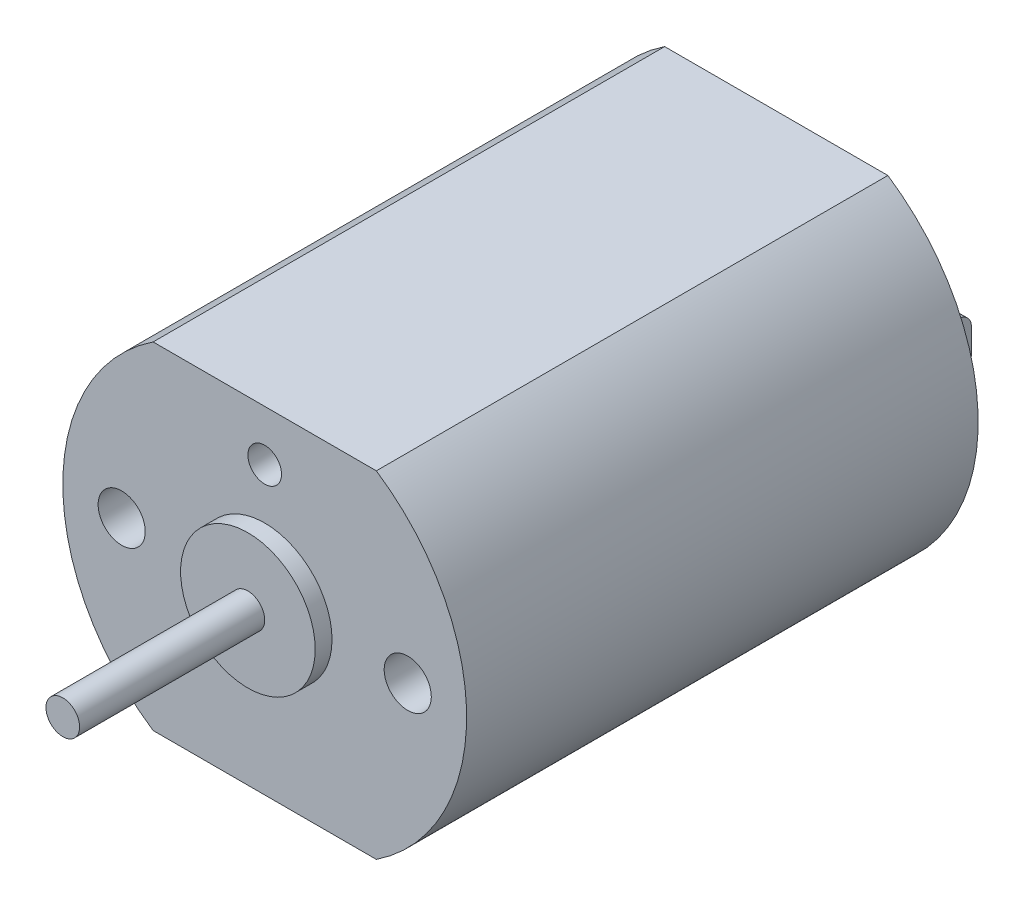
SolidWorks part; units mm, degrees
ref_plane "前视基准面" through (0, 0, 0) normal (0, 0, 1) x (1, 0, 0)
ref_plane "上视基准面" through (0, 0, 0) normal (0, 1, 0) x (1, 0, 0)
ref_plane "右视基准面" through (0, 0, 0) normal (1, 0, 0) x (0, 0, -1)
other "Configuration Table"
sketch "草图1" plane through (0, 0, 0) normal (0, 0, 1) x (1, 0, 0)
  line L0 (3.5, -0.75) -> (3.8, -0.75)
  line L1 (-6, -5) -> (6, -5)
  line L2 (-6, -5) -> (-6, 5)
  line L3 (-6, 5) -> (6, 5)
  line L4 (6, -5) -> (6, 5)
  line L5 (-6, -5) -> (6, 5) construction
  line L6 (-6, 5) -> (6, -5) construction
  line L7 (-3.8, -0.75) -> (-3.5, -0.75)
  line L8 (-3.8, -0.75) -> (-3.8, 0.75)
  line L9 (-3.8, 0.75) -> (-3.5, 0.75)
  line L10 (-3.5, -0.75) -> (-3.5, 0.75)
  line L11 (-3.8, -0.75) -> (-3.5, 0.75) construction
  line L12 (-3.8, 0.75) -> (-3.5, -0.75) construction
  line L13 (3.5, -0.75) -> (3.5, 0.75)
  line L14 (3.5, 0.75) -> (3.8, 0.75)
  line L15 (3.8, -0.75) -> (3.8, 0.75)
  line L16 (-3.5, 0) -> (3.5, 0) construction
  circle A0 centre (0, 0) radius 6
  circle A1 centre (0, 0) radius 2.5
  circle A2 centre (0, 0) radius 1.5
  point P0 (0, 0)
  point P8 (-3.65, 0)
  dimension "D6" = 5
  dimension "D7" = 3
  dimension "D1" = 12
  dimension "D2" = 10
  dimension "D3" = 0.3
  dimension "D4" = 1.5
  dimension "D5" = 7
extrude "凸台-拉伸1" add sketch "草图1" along normal blind 15.2 contours L3 A0 L1 A1 L15 L0 L13 L14 L10 L7 L8 L9 | A1 A2 | A2 | L0 L15 L14 L13 | L7 L10 L9 L8 region at (3.65, 0, 0) region at (-5.1491, -2.7634, 0) region at (-3.65, 0, 0) region at (-2.4293, 0, 0) region at (0, 0, 0)
extrude "凸台-拉伸2" add sketch "草图1<4>" against normal blind 2 contours L13 L14 L15 L0 | L8 L9 L10 L7
sketch "草图1<4>" plane through (0, 0, 0) normal (0, 0, 1) x (1, 0, 0) same geometry as "草图1"
sketch "草图2" plane through (3.8, 0, 0) normal (1, 0, 0) x (0, 0, -1)
  line L0 (0.95, 0) -> (1.05, 0) construction
  line L1 (0.95, 0.45) -> (1.05, 0.45)
  line L2 (0.95, -0.45) -> (1.05, -0.45)
  line L4 (1, 0.75) -> (1, -0.75) construction
  line L5 (2, 0.75) -> (0, 0.75) construction
  line L6 (2, -0.75) -> (0, -0.75) construction
  arc A0 (0.95, 0.45) -> (0.95, -0.45) centre (0.95, 0) ccw
  arc A1 (1.05, -0.45) -> (1.05, 0.45) centre (1.05, 0) ccw
  point P3 (1, 0)
  point P8 (0, 0)
  dimension "D2" = 0.45
  dimension "D1" = 0.1
extrude "切除-拉伸2" cut sketch "草图2" against normal through all
fillet "圆角1" radius 0.4 4 edges at (-3.65, 0.75, -2) (-3.65, -0.75, -2) (3.65, 0.75, -2) (3.65, -0.75, -2)
extrude "凸台-拉伸3" add sketch "草图1<5>" against normal blind 1.2 contours A1 A2 | A2 region at (-2.4293, 0, 0) region at (0, 0, 0)
sketch "草图1<5>" plane through (0, 0, 0) normal (0, 0, 1) x (1, 0, 0) same geometry as "草图1"
extrude "切除-拉伸1" cut sketch "草图1<7>" along normal blind 0.6 from surface contours A2 region at (0, 0, 0) starting at face at (2.5, 0, -1.2)
sketch "草图1<7>" plane through (0, 0, 0) normal (0, 0, 1) x (1, 0, 0) same geometry as "草图1"
fillet "圆角2" radius 0.4 1 edges at (2.5, 0, -1.2)
sketch "草图3" plane through (0, 0, 15.2) normal (0, 0, 1) x (1, 0, 0)
  circle A0 centre (0, 0) radius 2
  circle A1 centre (0, 0) radius 0.5
  dimension "D1" = 4
  dimension "D2" = 1
extrude "凸台-拉伸4" add sketch "草图3" along normal blind 0.5 contours A0
extrude "凸台-拉伸5" add sketch "草图3<3>" along normal blind 6 contours A1 region at (0, 0, 15.2)
sketch "草图3<3>" plane through (0, 0, 15.2) normal (0, 0, 1) x (1, 0, 0) same geometry as "草图3"
sketch "草图4" plane through (0, 0, 15.2) normal (0, 0, 1) x (1, 0, 0)
  line L0 (-4.25, 0) -> (4.25, 0) construction
  line L1 (0, 0) -> (0, 5) construction
  line L2 (-3.3166, 5) -> (3.3166, 5) construction
  circle A0 centre (-4.25, 0) radius 0.7
  circle A1 centre (4.25, 0) radius 0.7
  circle A2 centre (0, 3.5) radius 0.5
  point P6 (0, 0)
  dimension "D1" = 1.4
  dimension "D2" = 8.5
  dimension "D3" = 1
  dimension "D4" = 3.5
extrude "切除-拉伸3" cut sketch "草图4" against normal blind 1
